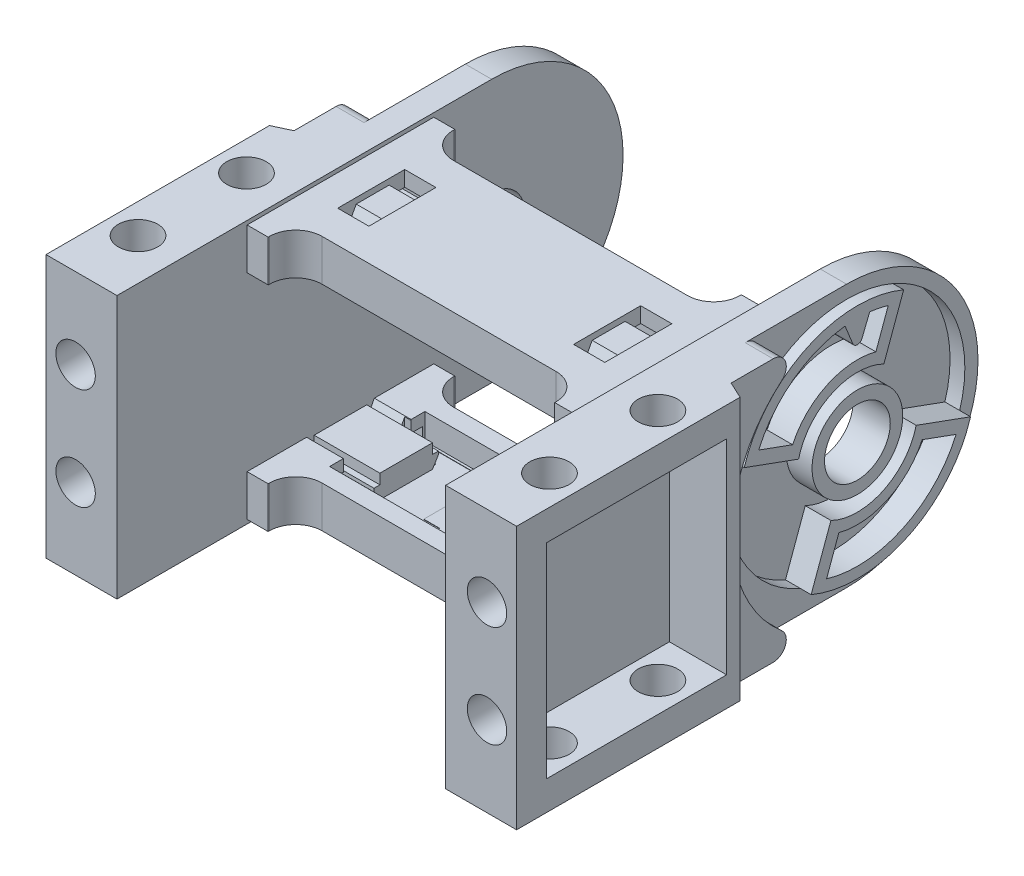
SolidWorks part; units mm, degrees
material "ABS"
ref_plane "Front Plane" through (0, 0, 0) normal (0, 0, 1) x (1, 0, 0)
ref_plane "Top Plane" through (0, 0, 0) normal (0, 1, 0) x (1, 0, 0)
ref_plane "Right Plane" through (0, 0, 0) normal (1, 0, 0) x (0, 0, -1)
other "Configuration Table"
ref_plane "Plane1" through (31.25, 0, 0) normal (1, 0, 0) x (0, 0, -1)
sketch "Sketch1" plane through (31.25, 0, 0) normal (1, 0, 0) x (0, 0, -1)
  line L0 (0, 0) -> (46, 0) construction
  line L1 (-11, 20) -> (30.5828, 20)
  line L2 (-11, -20) -> (30.5828, -20)
  line L3 (46, 26.3266) -> (46, -25.6565) construction
  line L4 (-11, -20) -> (-11, 20)
  arc A7 (31.8838, 16.481) -> (31.8838, -16.481) centre (46, 0) ccw
  arc A8 (30.5828, -20) -> (31.8838, -16.481) centre (30.5828, -18) ccw
  arc A9 (31.8838, 16.481) -> (30.5828, 20) centre (30.5828, 18) ccw
  dimension "D2" = 40
  dimension "D4" = 21.7
  dimension "D5" = 2
  dimension "D1" = 46
  dimension "D6" = 57
extrude "Boss-Extrude1" add sketch "Sketch1" along normal blind 2
sketch "Sketch3" plane through (31.25, 0, 0) normal (-1, 0, 0) x (0, 0, 1)
  line L3 (11, -20) -> (11, 20)
  line L4 (-30.5828, -20) -> (11, -20)
  line L5 (11, 20) -> (-30.5828, 20)
  line L6 (-30.5828, -20) -> (11, -20)
  line L7 (11, 20) -> (-30.5828, 20)
  line L8 (11, -20) -> (11, 20)
  arc A8 (-30.5828, 20) -> (-31.8838, 16.481) centre (-30.5828, 18) ccw
  arc A10 (-30.5828, 20) -> (-31.8838, 16.481) centre (-30.5828, 18) ccw
  arc A11 (-31.8838, -16.481) -> (-31.8838, 16.481) centre (-46, 0) ccw
  arc A17 (-31.8838, -16.481) -> (-31.8838, 16.481) centre (-46, 0) ccw
  arc A18 (-31.8838, -16.481) -> (-30.5828, -20) centre (-30.5828, -18) ccw
  arc A19 (-31.8838, -16.481) -> (-30.5828, -20) centre (-30.5828, -18) ccw
  dimension "D1" = 0
extrude "Boss-Extrude3" add sketch "Sketch3" along normal blind 2.25
sketch "Sketch6" plane through (29, 0, 0) normal (1, 0, 0) x (0, 0, -1)
  line L0 (13.3327, 20) -> (46, 20)
  line L1 (13.3327, -20) -> (46, -20)
  line L2 (46, 0) -> (0, 0) construction
  line L3 (30.5828, 20) -> (-11, 20) construction
  line L4 (-11, -20) -> (30.5828, -20) construction
  line L5 (-20, 0) -> (0, 0) construction
  arc A1 (46, -20) -> (46, 20) centre (46, 0) ccw
  arc A2 (12.1422, -16.3929) -> (12.1422, 16.3929) centre (0, 0) ccw
  arc A3 (13.3327, -20) -> (12.1422, -16.3929) centre (13.3327, -18) cw
  arc A4 (13.3327, 20) -> (12.1422, 16.3929) centre (13.3327, 18) ccw
  circle A5 centre (46, 0) radius 5
  point P19 (4.02, -20)
  point P22 (4.02, 20)
  dimension "D2" = 40.4
  dimension "D3" = 2
  dimension "D4" = 10
  dimension "D1" = 46
  dimension "D5" = 66
extrude "Boss-Extrude5" add sketch "Sketch6" against normal blind 4
sketch "Sketch7" plane through (29, 0, 0) normal (1, 0, 0) x (0, 0, -1)
  circle A0 centre (46, 0) radius 18
  arc A2 (46, -20) -> (46, 20) centre (46, 0) ccw construction
  dimension "D1" = 2
extrude "Cut-Extrude1" cut sketch "Sketch7" against normal blind 2.25
sketch "Sketch8" plane through (26.75, 0, 0) normal (1, 0, 0) x (0, 0, -1)
  line L0 (50.6899, 15.6629) -> (48.8125, 10.505)
  line L1 (53.0405, 16.566) -> (50.0311, 8.2977)
  line L2 (44.2899, -4.6985) -> (47.7101, 4.6985) construction
  line L3 (46, 0) -> (73.2087, 0) construction
  line L4 (46, 0) -> (41.3015, 1.7101) construction
  line L5 (37.0525, 2.2457) -> (28.7842, 5.2551)
  line L6 (30.9869, 6.4753) -> (36.1448, 4.598)
  line L7 (46, 0) -> (41.4685, -2.1131) construction
  line L8 (41.3101, -15.6629) -> (43.1875, -10.505)
  line L9 (41.9689, -8.2977) -> (38.9595, -16.566)
  line L10 (63.2158, -5.2551) -> (54.9475, -2.2457)
  line L11 (61.0131, -6.4753) -> (55.8552, -4.598)
  circle A0 centre (46, 0) radius 5
  circle A1 centre (46, 0) radius 6.9
  circle A2 centre (46, 0) radius 5 construction
  arc A3 (50.0311, 8.2977) -> (37.0525, 2.2457) centre (46, 0) ccw
  arc A6 (53.0405, 16.566) -> (28.7842, 5.2551) centre (46, 0) ccw
  circle A8 centre (46, 0) radius 18 construction
  arc A9 (48.8125, 10.505) -> (36.1448, 4.598) centre (46, 0) ccw
  arc A10 (50.6899, 15.6629) -> (30.9869, 6.4753) centre (46, 0) ccw
  arc A11 (61.0131, -6.4753) -> (41.3101, -15.6629) centre (46, 0) cw
  arc A12 (55.8552, -4.598) -> (43.1875, -10.505) centre (46, 0) cw
  arc A13 (63.2158, -5.2551) -> (38.9595, -16.566) centre (46, 0) cw
  arc A14 (54.9475, -2.2457) -> (41.9689, -8.2977) centre (46, 0) cw
  dimension "D1" = 13.8
  dimension "D2" = 18.45
  dimension "D5" = 70
  dimension "D6" = 1.9
  dimension "D7" = 90
  dimension "D8" = 1.9
  dimension "D4" = 1.65
  dimension "D3" = 1.65
  dimension "D9" = 45
extrude "Boss-Extrude6" add sketch "Sketch8" along normal blind 3.9
sketch "Sketch9" plane through (30.65, 0, 0) normal (1, 0, 0) x (0, 0, -1)
  line L0 (46, 0) -> (46, 18) construction
  line L1 (44.125, 16.2421) -> (45.3045, 13.3193)
  line L2 (47.875, 16.2421) -> (46.6955, 13.3193)
  arc A0 (53.0405, 16.566) -> (28.7842, 5.2551) centre (46, 0) ccw construction
  arc A1 (50.6899, 15.6629) -> (30.9869, 6.4753) centre (46, 0) ccw construction
  arc A2 (45.3045, 13.3193) -> (46.6955, 13.3193) centre (46, 13.6) ccw
  arc A3 (44.125, 16.2421) -> (47.875, 16.2421) centre (46, 0) cw
  dimension "D1" = 0.75
  dimension "D2" = 3.5
  dimension "D3" = 3.75
extrude "Boss-Extrude7" add sketch "Sketch9" against normal up to next
sketch "Sketch11" plane through (25, 0, 0) normal (-1, 0, 0) x (0, 0, 1)
  line L0 (-23, 0) -> (-23, 21.8907) construction
  line L3 (-46, 0) -> (0, 0) construction
  line L4 (-27, 13.4) -> (-27, 14.94)
  line L5 (-27, 13.4) -> (-19, 13.4)
  line L6 (-27, 14.94) -> (-27.9, 14.94)
  line L7 (-27.9, 14.94) -> (-27.9, 15.44)
  line L8 (-27.9, 15.44) -> (-27, 16.9)
  line L9 (-27, 16.9) -> (-19, 16.9)
  line L10 (-18.1, 15.44) -> (-19, 16.9)
  line L11 (-18.1, 14.94) -> (-18.1, 15.44)
  line L12 (-19, 14.94) -> (-18.1, 14.94)
  line L13 (-19, 13.4) -> (-19, 14.94)
  line L14 (-19, -13.4) -> (-19, -14.94)
  line L15 (-19, -14.94) -> (-18.1, -14.94)
  line L16 (-18.1, -14.94) -> (-18.1, -15.44)
  line L17 (-18.1, -15.44) -> (-19, -16.9)
  line L18 (-27, -16.9) -> (-19, -16.9)
  line L19 (-27.9, -15.44) -> (-27, -16.9)
  line L20 (-27.9, -14.94) -> (-27.9, -15.44)
  line L21 (-27, -14.94) -> (-27.9, -14.94)
  line L22 (-27, -13.4) -> (-19, -13.4)
  line L23 (-27, -13.4) -> (-27, -14.94)
  dimension "D1" = 1.54
  dimension "D2" = 26.8
  dimension "D3" = 33.8
  dimension "D4" = 8
  dimension "D5" = 9.8
  dimension "D6" = 0.5
extrude "Boss-Extrude8" add sketch "Sketch11" along normal blind 10
sketch "Sketch13" plane through (0, 16.9, 0) normal (0, 1, 0) x (1, 0, 0)
  line L0 (15.8, 30.3851) -> (15.8, 15.9317) construction
  line L1 (15, 19) -> (15, 27) construction
  dimension "D1" = 0.8
ref_plane "Plane3" through (15.8, 0, 0) normal (-1, 0, 0) x (0, 0, 1)
sketch "Sketch15" plane through (15.8, 0, 0) normal (-1, 0, 0) x (0, 0, 1)
  line L0 (-23, 13.4) -> (-23, 20.5432) construction
  line L1 (-27, 13.4) -> (-19, 13.4) construction
  line L2 (-25.5, 18.75) -> (-20.5, 18.75)
  line L3 (-20.5, 18.75) -> (-19.5, 16.9)
  line L4 (-30.3851, 16.9) -> (-15.9317, 16.9) construction
  line L5 (-19.5, 16.9) -> (-26.5, 16.9)
  line L6 (-25.5, 18.75) -> (-26.5, 16.9)
  line L7 (-46, 20) -> (-13.3327, 20) construction
  dimension "D1" = 7
  dimension "D2" = 5
  dimension "D3" = 1.85
  dimension "D4" = 1.25
extrude "Boss-Extrude9" add sketch "Sketch15" against normal blind 4.3
extrude "Boss-Extrude11" add sketch "Эскиз1<2>" against normal up to surface (6.25 mm away) up to face at (25, 15.124, -23)
sketch "Эскиз1<2>" plane through (31.25, 0, 0) normal (1, 0, 0) x (0, 0, -1) same geometry as "Sketch1"
sketch "Sketch22" plane through (0, 20, 0) normal (0, 1, 0) x (1, 0, 0)
  line L0 (33.25, -11) -> (35.8, -11)
  line L1 (35.8, -11) -> (35.8, 23)
  line L2 (35.8, 23) -> (33.25, 24.1891)
  line L3 (33.25, 30.5828) -> (33.25, -11) construction
  line L4 (33.25, 24.1891) -> (33.25, -11)
  line L5 (25, 46) -> (25, -11) construction
  dimension "D1" = 10.8
  dimension "D2" = 34
  dimension "D3" = 115
extrude "Boss-Extrude12" add sketch "Sketch22" against normal up to surface (40 mm away) up to face at (29.0833, -20, -21.8609)
sketch "Sketch23" plane through (35.8, 0, 0) normal (1, 0, 0) x (0, 0, -1)
  line L0 (-11, 20) -> (23, 20) construction
  line L1 (-6.45, 15.55) -> (20.95, 15.55)
  line L2 (-6.45, 15.55) -> (-6.45, -15.55)
  line L3 (-6.45, -15.55) -> (20.95, -15.55)
  line L4 (20.95, 15.55) -> (20.95, -15.55)
  line L5 (23, -20) -> (-11, -20) construction
  line L6 (-11, -20) -> (-11, 20) construction
  dimension "D1" = 4.45
  dimension "D2" = 4.45
  dimension "D3" = 4.55
  dimension "D4" = 27.4
extrude "Cut-Extrude7" cut sketch "Sketch23" against normal blind 8.7
sketch "Sketch24" plane through (0, -20, 0) normal (0, -1, 0) x (1, 0, 0)
  line L0 (35.8, 11) -> (25, 11) construction
  line L1 (35.8, -23) -> (35.8, 11) construction
  circle A0 centre (31.3, 1.5) radius 3
  circle A1 centre (31.3, -15) radius 3
  dimension "D4" = 6
  dimension "D1" = 9.5
  dimension "D2" = 16.5
  dimension "D3" = 4.5
extrude "Cut-Extrude8" cut sketch "Sketch24" against normal through all
sketch "Sketch25" plane through (0, 0, 11) normal (0, 0, 1) x (1, 0, 0)
  line L0 (31.3, -20) -> (31.3, 20) construction
  line L1 (35.8, -20) -> (25, -20) construction
  line L2 (35.8, 20) -> (25, 20) construction
  line L3 (35.8, -20) -> (35.8, 20) construction
  line L4 (31.3, 0) -> (25, 0) construction
  line L5 (25, -20) -> (25, 20) construction
  circle A0 centre (31.3, -7.75) radius 3
  circle A1 centre (31.3, 7.75) radius 3
  dimension "D2" = 6
  dimension "D3" = 15.5
  dimension "D1" = 4.5
extrude "Cut-Extrude9" cut sketch "Sketch25" against normal up to next
mirror "Mirror1" about plane through (0, 0, 0) normal (0, 1, 0) of "Boss-Extrude9"
mirror "Mirror2" about plane through (0, 0, 0) normal (1, 0, 0) of bodies 114
ref_plane "Plane2" through (0, 19.4, 0) normal (0, 1, 0) x (1, 0, 0)
sketch "Sketch17" plane through (0, 19.4, 0) normal (0, 1, 0) x (1, 0, 0)
  line L0 (0, 0) -> (0, 46) construction
  line L1 (-25, 23) -> (25, 23) construction
  line L2 (-25, 19) -> (-25, 27) construction
  line L3 (25, 19) -> (25, 27) construction
  line L4 (21.8, 9) -> (21.8, 8.8)
  line L5 (17.8, 13) -> (-17.8, 13)
  line L7 (17.8, 33) -> (-17.8, 33)
  line L9 (21.8, 13) -> (-21.8, 33) construction
  line L10 (21.8, 33) -> (-21.8, 13) construction
  line L11 (21.8, 37.2) -> (25, 37.2)
  line L12 (21.8, 37.2) -> (21.8, 37)
  line L13 (21.8, 8.8) -> (25, 8.8)
  line L14 (25, 37.2) -> (25, 8.8)
  line L15 (-25, 37.2) -> (-25, 8.8)
  line L16 (-21.8, 8.8) -> (-25, 8.8)
  line L17 (-21.8, 37.2) -> (-21.8, 37)
  line L18 (-21.8, 37.2) -> (-25, 37.2)
  line L19 (-21.8, 9) -> (-21.8, 8.8)
  line L20 (-15.8, 25.5) -> (-20.1, 20.5) construction
  line L21 (20.325, 17.9) -> (15.575, 17.9)
  line L22 (-20.325, 17.9) -> (-15.575, 17.9)
  line L23 (-20.325, 17.9) -> (-20.325, 28.1)
  line L24 (-20.325, 28.1) -> (-15.575, 28.1)
  line L25 (-15.575, 17.9) -> (-15.575, 28.1)
  line L26 (-20.325, 17.9) -> (-15.575, 28.1) construction
  line L27 (-20.325, 28.1) -> (-15.575, 17.9) construction
  line L28 (15.575, 17.9) -> (15.575, 28.1)
  line L29 (20.325, 17.9) -> (20.325, 28.1)
  line L30 (20.325, 28.1) -> (15.575, 28.1)
  arc A0 (21.8, 37) -> (17.8, 33) centre (17.8, 37) cw
  arc A1 (17.8, 13) -> (21.8, 9) centre (17.8, 9) cw
  arc A2 (-17.8, 13) -> (-21.8, 9) centre (-17.8, 9) ccw
  arc A3 (-17.8, 33) -> (-21.8, 37) centre (-17.8, 37) cw
  point P4 (0, 23)
  point P10 (0, 23)
  point P39 (-17.95, 23)
  point P40 (-17.95, 23)
  dimension "D5" = 4
  dimension "D1" = 28.4
  dimension "D2" = 3.2
  dimension "D3" = 20
  dimension "D4" = 50
  dimension "D6" = 10.2
  dimension "D7" = 4.75
extrude "Boss-Extrude10" add sketch "Sketch17" against normal blind 6.3 separate body
sketch "Sketch18" plane through (25, 0, 0) normal (1, 0, 0) x (0, 0, -1)
  line L0 (23, 13.1) -> (23, 19.4) construction
  line L1 (8.8, 13.1) -> (37.2, 13.1) construction
  line L2 (4.5375, 19.4) -> (-4.5375, 19.4) construction
  line L4 (29.89, 14.9) -> (16.11, 14.9)
  line L5 (29.89, 14.9) -> (29.89, 17.05)
  line L6 (29.89, 17.05) -> (16.11, 17.05)
  line L7 (16.11, 14.9) -> (16.11, 17.05)
  line L8 (29.89, 14.9) -> (16.11, 17.05) construction
  line L9 (29.89, 17.05) -> (16.11, 14.9) construction
  point P6 (23, 15.975)
  dimension "D1" = 13.78
  dimension "D2" = 2.15
  dimension "D3" = 2.35
extrude "Cut-Extrude3" cut sketch "Sketch18" against normal blind 15.8
sketch "Sketch19" plane through (25, 0, 0) normal (1, 0, 0) x (0, 0, -1)
  line L0 (23, 14.9) -> (23, 13.1) construction
  line L1 (16.11, 14.9) -> (29.89, 14.9) construction
  line L2 (8.8, 13.1) -> (37.2, 13.1) construction
  line L3 (18.8, 14.9) -> (17.85, 13.1)
  line L4 (17.85, 13.1) -> (28.15, 13.1)
  line L5 (28.15, 13.1) -> (27.2, 14.9)
  line L6 (27.2, 14.9) -> (18.8, 14.9)
  dimension "D1" = 10.3
  dimension "D2" = 8.4
extrude "Cut-Extrude4" cut sketch "Sketch19" against normal blind 11.25
sketch "Sketch20" plane through (0, 13.1, 0) normal (0, -1, 0) x (1, 0, 0)
  line L0 (13.75, -23) -> (13.5581, -23) construction
  line L1 (13.75, -17.85) -> (13.75, -28.15) construction
  line L2 (6.75, -27.125) -> (6.75, -26.125)
  line L3 (13.75, -18.875) -> (6.75, -18.875)
  line L4 (13.75, -18.875) -> (13.75, -19.875)
  line L5 (13.75, -19.875) -> (6.75, -19.875)
  line L6 (6.75, -18.875) -> (6.75, -19.875)
  line L7 (13.75, -26.125) -> (6.75, -26.125)
  line L8 (13.75, -27.125) -> (13.75, -26.125)
  line L9 (13.75, -27.125) -> (6.75, -27.125)
  dimension "D1" = 6.25
  dimension "D2" = 8.25
  dimension "D3" = 7
extrude "Cut-Extrude5" cut sketch "Sketch20" against normal up to surface (3.95 mm away) up to face at (17.1, 17.05, -23)
mirror "Mirror5" about plane through (0, 0, 0) normal (1, 0, 0) of "Cut-Extrude5", "Cut-Extrude4", "Cut-Extrude3"
sketch "Sketch21" plane through (0, 13.1, 0) normal (0, -1, 0) x (1, 0, 0)
  line L0 (0, -13) -> (0, -33) construction
  line L1 (-17.8, -13) -> (17.8, -13) construction
  line L2 (17.8, -33) -> (-17.8, -33) construction
  line L4 (19.4, -30.25) -> (-19.4, -30.25)
  line L5 (19.4, -30.25) -> (19.4, -15.75)
  line L6 (19.4, -15.75) -> (-19.4, -15.75)
  line L7 (-19.4, -30.25) -> (-19.4, -15.75)
  line L8 (19.4, -30.25) -> (-19.4, -15.75) construction
  line L9 (19.4, -15.75) -> (-19.4, -30.25) construction
  point P6 (0, -23)
  dimension "D1" = 38.8
  dimension "D2" = 14.5
extrude "Cut-Extrude6" cut sketch "Sketch21" against normal blind 3.9
mirror "Mirror4" about plane through (0, 0, 0) normal (0, 1, 0) of bodies 122 116
equation "\"D8@Sketch8\" = \"D6@Sketch8\""
equation "\"D3@Sketch8\" = \"D4@Sketch8\""
equation "\"D2@Sketch23\" = \"D1@Sketch23\""
